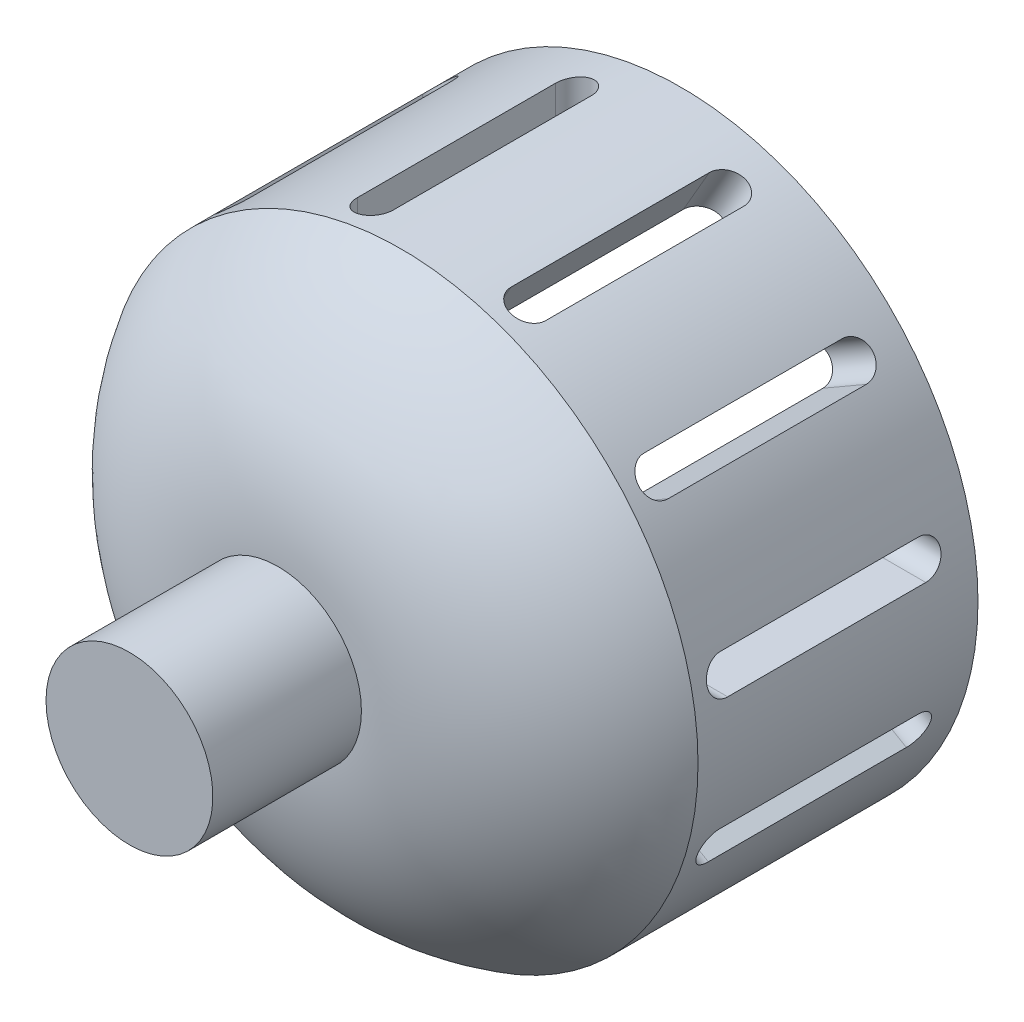
SolidWorks part; units mm, degrees
material "ABS"
ref_plane "Front Plane" through (0, 0, 0) normal (0, 0, 1) x (1, 0, 0)
ref_plane "Top Plane" through (0, 0, 0) normal (0, 1, 0) x (1, 0, 0)
ref_plane "Right Plane" through (0, 0, 0) normal (1, 0, 0) x (0, 0, -1)
sketch "Sketch1" plane through (0, 0, 0) normal (0, 0, 1) x (1, 0, 0)
  circle A0 centre (0, 0) radius 10.7
  dimension "D1" = 21.4
extrude "Boss-Extrude1" add sketch "Sketch1" along normal blind 19.05
sketch "Sketch2" plane through (0, 0, 0) normal (0, 1, 0) x (1, 0, 0)
  line L0 (0, -70.3648) -> (0, 69.8669) construction
  line L1 (0, 0) -> (10.7, 0)
  line L5 (38.1, 51.668) -> (38.1, 15.7649)
  line L6 (0, 51.668) -> (38.1, 51.668)
  line L7 (0, 51.668) -> (0, 0)
  arc A1 (10.7, 0) -> (38.1, 15.7649) centre (10.7, 31.6936) ccw
  dimension "D1" = 38.1
revolve "Revolve1" add sketch "Sketch2" angle 360 about L0
sketch "Sketch3" plane through (0, 0, -51.668) normal (0, 0, -1) x (-1, 0, 0)
  circle A0 centre (0, 0) radius 34.925
ref_plane "Plane4" through (38.1, 0, 0) normal (1, 0, 0) x (0, 0, -1)
sketch "Sketch5" plane through (38.1, 0, 0) normal (1, 0, 0) x (0, 0, -1)
  line L0 (0, 0) -> (65.6292, 0) construction
  line L1 (19.918, 7.4392) -> (45.318, 7.4392) construction
  line L2 (19.918, 9.7386) -> (45.318, 9.7386)
  line L3 (19.918, 5.1398) -> (45.318, 5.1398)
  line L4 (51.668, -38.1) -> (51.668, 38.1) construction
  arc A0 (19.918, 9.7386) -> (19.918, 5.1398) centre (19.918, 7.4392) ccw
  arc A1 (45.318, 5.1398) -> (45.318, 9.7386) centre (45.318, 7.4392) ccw
  point P5 (32.618, 7.4392)
  dimension "D3" = 2.2994
  dimension "D1" = 6.35
  dimension "D2" = 25.4
sketch "Sketch6" plane through (0, 0, 0) normal (0, 1, 0) x (1, 0, 0)
  line L0 (0, 0) -> (0, 60.1738) construction
  line L5 (-10.7, 0) -> (0, 0) construction
  line L6 (-31.75, 51.7553) -> (0, 51.7553)
  line L8 (0, 6.35) -> (-10.7, 6.35)
  line L9 (-31.75, 51.7553) -> (-31.75, 15.7649)
  line L10 (38.1, 15.7649) -> (-38.1, 15.7649) construction
  line L11 (-38.1, 51.668) -> (-38.1, 15.7649) construction
  line L12 (0, 51.7553) -> (0, 6.35)
  spline S0 degree 2 poles (-31.75, 15.7649) (-23.6175, 5.8618) (-10.7, 6.35) knots 0 0 0 1 1 1
  dimension "D1" = 6.35
  dimension "D2" = 6.35
revolve "Cut-Revolve3" cut sketch "Sketch6" angle 360 about L0
extrude "Cut-Extrude3" cut sketch "Sketch5" against normal up to next and the other way through all
ref_axis "axis vacuum gripper" through (0, 0, -183.6744) along (0, 0, 1)
pattern_circular "CirPattern1" count 12 over 360 about axis through (0, 0, -183.6744) along (0, 0, 1) of "Cut-Extrude3"
